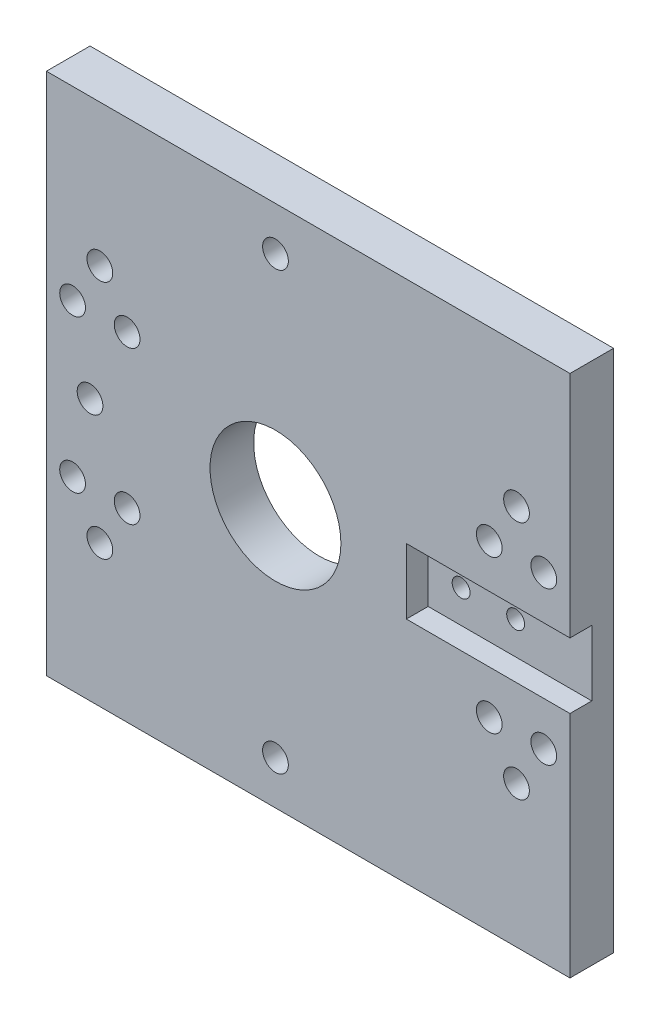
SolidWorks part; units mm, degrees
ref_plane "Alzado" through (0, 0, 0) normal (0, 0, 1) x (1, 0, 0)
ref_plane "Planta" through (0, 0, 0) normal (0, 1, 0) x (1, 0, 0)
ref_plane "Vista lateral" through (0, 0, 0) normal (1, 0, 0) x (0, 0, -1)
sketch "Croquis1" plane through (0, 0, 0) normal (0, 0, 1) x (1, 0, 0)
  line L1 (-67.5, 60) -> (67.5, 60)
  line L2 (-67.5, 60) -> (-67.5, -60)
  line L3 (-67.5, -60) -> (67.5, -60)
  line L4 (67.5, 60) -> (67.5, -60)
  line L5 (-67.5, 60) -> (67.5, -60) construction
  line L6 (-67.5, -60) -> (67.5, 60) construction
  line L7 (67.5, 7.5) -> (30, 7.5)
  line L8 (67.5, 7.5) -> (67.5, -7.5)
  line L9 (67.5, -7.5) -> (30, -7.5)
  line L10 (30, 7.5) -> (30, -7.5)
  line L11 (-67.5, 60) -> (-52.5, 60)
  line L12 (-67.5, 60) -> (-67.5, -60)
  line L13 (-67.5, -60) -> (-52.5, -60)
  line L14 (-52.5, 60) -> (-52.5, -60)
  circle A0 centre (0, 0) radius 15
  circle A1 centre (37.55, 0) radius 2.05
  circle A2 centre (50.05, 0) radius 2.05
  point P0 (0, 0)
  point P12 (30, 0)
  point P13 (67.5, 0)
  dimension "D3" = 30
  dimension "D6" = 7.55
  dimension "D7" = 12.5
  dimension "D8" = 4.1
  dimension "D1" = 135
  dimension "D2" = 120
  dimension "D4" = 15
  dimension "D5" = 37.5
  dimension "D9" = 15
extrude "Saliente-Extruir1" add sketch "Croquis1" along normal blind 5 contours L10 L7 L4 L1 L2 L3 L9 A0 | L7 L10 L9 L4 A2 A1 region at (7.5, 58.3029, 0) region at (67.0961, 0, 0)
extrude "Saliente-Extruir2" add sketch "Croquis1<4>" along normal offset from surface (10 mm away) 5 contours L10 L7 L4 L1 L2 L3 L9 A0 region at (7.5, 58.3029, 0) up to face at (7.5, 0, 5) offset beyond the face yes
sketch "Croquis1<4>" plane through (0, 0, 0) normal (0, 0, 1) x (1, 0, 0) same geometry as "Croquis1"
sketch "Croquis2" plane through (0, 0, 10) normal (0, 0, 1) x (1, 0, 0)
  line L0 (49, 17.5) -> (61.5, 17.5) construction
  line L1 (67.5, 60) -> (67.5, 7.5) construction
  line L2 (7.5, 60) -> (7.5, -60) construction
  line L3 (67.5, 7.5) -> (30, 7.5) construction
  line L4 (0, 0) -> (100.8416, 0) construction
  line L5 (49, -17.5) -> (61.5, -17.5) construction
  line L6 (-52.5, 60) -> (-52.5, -60) construction
  line L7 (-52.5, 60) -> (67.5, 60) construction
  line L8 (-52.5, -60) -> (67.5, -60) construction
  circle A0 centre (49, 17.5) radius 2.95
  circle A1 centre (55.25, 27.5) radius 2.95
  circle A2 centre (61.5, 17.5) radius 2.95
  circle A3 centre (61.5, -17.5) radius 2.95
  circle A4 centre (55.25, -27.5) radius 2.95
  circle A5 centre (49, -17.5) radius 2.95
  circle A6 centre (-42.5, 0) radius 2.95
  circle A7 centre (0, 50) radius 2.95
  circle A9 centre (0, -50) radius 2.95
  circle A10 centre (-40.25, -27.5) radius 2.95
  circle A11 centre (-46.5, -17.5) radius 2.95
  circle A12 centre (-34, -17.5) radius 2.95
  circle A13 centre (-34, 17.5) radius 2.95
  circle A14 centre (-46.5, 17.5) radius 2.95
  circle A15 centre (-40.25, 27.5) radius 2.95
  point P5 (55.25, 17.5)
  dimension "D1" = 5.9
  dimension "D6" = 5.9
  dimension "D7" = 10
  dimension "D8" = 10
  dimension "D2" = 12.5
  dimension "D3" = 6
  dimension "D4" = 10
  dimension "D5" = 10
extrude "Cortar-Extruir1" cut sketch "Croquis2" against normal through all
